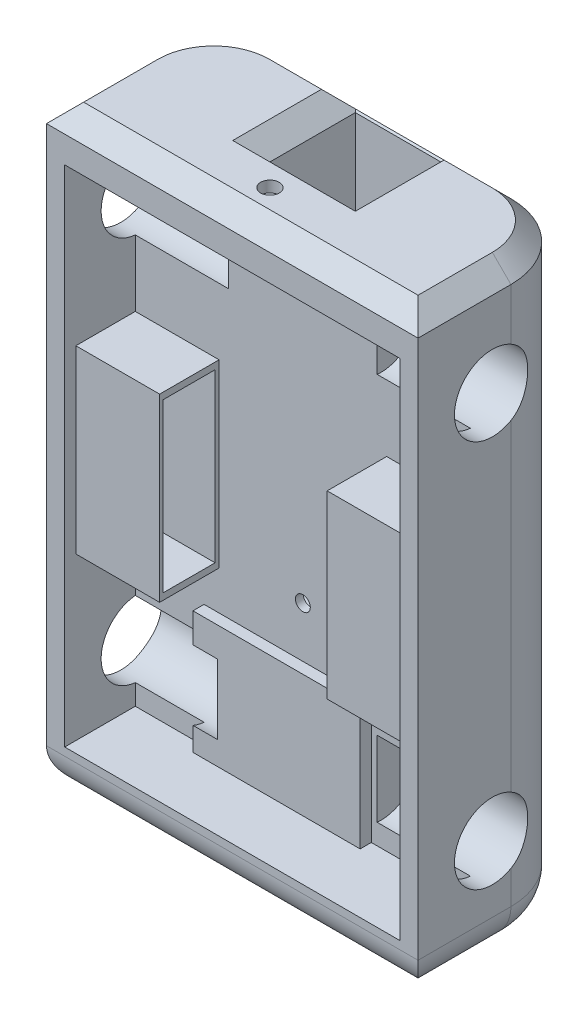
SolidWorks part; units mm, degrees
ref_plane "Front Plane" through (0, 0, 0) normal (0, 0, 1) x (1, 0, 0)
ref_plane "Top Plane" through (0, 0, 0) normal (0, 1, 0) x (1, 0, 0)
ref_plane "Right Plane" through (0, 0, 0) normal (1, 0, 0) x (0, 0, -1)
sketch "Sketch1" plane through (0, 0, 0) normal (0, 0, 1) x (1, 0, 0)
  line L16 (-50, 80) -> (50, 80)
  line L17 (-50, 80) -> (-50, -80)
  line L18 (-50, -80) -> (50, -80)
  line L19 (50, 80) -> (50, -80)
  line L20 (-50, 80) -> (50, -80) construction
  line L21 (-50, -80) -> (50, 80) construction
  point P0 (0, 0)
  point P3 (0, 0)
  point P6 (0, 0)
extrude "Boss-Extrude1" add sketch "Sketch1" along normal blind 20
ref_plane "Plane1" through (0, 80, 0) normal (0, 1, 0) x (1, 0, 0)
sketch "Sketch5" plane through (0, 80, 0) normal (0, 1, 0) x (1, 0, 0)
  line L1 (50, 0) -> (-50, 0)
  line L2 (50, 0) -> (50, 5)
  line L3 (30, 25) -> (-30, 25)
  line L4 (-50, 0) -> (-50, 5)
  arc A0 (-30, 25) -> (-50, 5) centre (-30, 5) ccw
  arc A1 (50, 5) -> (30, 25) centre (30, 5) ccw
  point P8 (-50, 25)
  point P11 (50, 25)
  dimension "D3" = 20
  dimension "D1" = 25
  dimension "D2" = 100
extrude "Boss-Extrude2" add sketch "Sketch5" against normal blind 160 contours A1 L3 A0 L4 L1 L2
fillet "Fillet4" radius 10 6 edges at (0, -80, 20) (50, -80, 7.5) (44.1421, -80, -19.1421) (0, -80, -25) (-44.1421, -80, -19.1421) (-50, -80, 7.5)
sketch "Sketch11" plane through (0, 0, 20) normal (0, 0, 1) x (1, 0, 0)
  line L1 (45.092, 67.8431) -> (-45.092, 67.8431)
  line L2 (45.092, 67.8431) -> (45.092, -67.8431)
  line L3 (45.092, -67.8431) -> (-45.092, -67.8431)
  line L4 (-45.092, 67.8431) -> (-45.092, -67.8431)
  line L5 (45.092, 67.8431) -> (-45.092, -67.8431) construction
  line L6 (45.092, -67.8431) -> (-45.092, 67.8431) construction
  point P0 (0, 0)
extrude "Cut-Extrude3" cut sketch "Sketch11" against normal blind 19 contours L2 L3 L4 L1
sketch "Sketch12" plane through (0, 80, 0) normal (0, 1, 0) x (1, 0, 0)
  line L0 (0, -20) -> (0, 25) construction
  line L1 (50, -20) -> (-50, -20) construction
  line L2 (30, 25) -> (-30, 25) construction
  line L3 (50, 2.5) -> (-50, 2.5) construction
  line L4 (50, -20) -> (50, 5) construction
  line L5 (-50, -20) -> (-50, 5) construction
  line L11 (12, 1.1277) -> (-11, 1.1277)
  line L12 (12, 1.1277) -> (12, 24.1277)
  line L13 (12, 24.1277) -> (-11, 24.1277)
  line L14 (-11, 1.1277) -> (-11, 24.1277)
  line L15 (12, 1.1277) -> (-11, 24.1277) construction
  line L16 (12, 24.1277) -> (-11, 1.1277) construction
  point P13 (0.5, 12.6277)
  dimension "D1" = 23
  dimension "D2" = 23
extrude "Cut-Extrude4" cut sketch "Sketch12" against normal blind 110 contours L12 L13 L14 L11
sketch "Sketch13" plane through (0, 0, -25) normal (0, 0, -1) x (-1, 0, 0)
  line L0 (0, 0) -> (0, 80) construction
  line L1 (26.3419, 80) -> (-26.3419, 80) construction
  line L2 (0, 0) -> (30, 0) construction
  line L3 (30, -70) -> (30, 80) construction
  ellipse E0 centre (0, 40) end of major axis (0, 24.536) minor radius 8.1947
extrude "Cut-Extrude5" cut sketch "Sketch13" against normal blind 4
sketch "Sketch14" plane through (50, 0, 0) normal (1, 0, 0) x (0, 0, -1)
  line L0 (0, -52.1971) -> (0, 0) construction
  line L5 (-20, 0) -> (0, 0) construction
  line L6 (-20, -70) -> (-20, 80) construction
  line L7 (0, -35) -> (-20, -35) construction
  circle A0 centre (0, -52.1971) radius 10.2
  circle A1 centre (0, 52.1971) radius 10.2
sketch "Sketch15" plane through (0, 0, -1.1277) normal (0, 0, -1) x (-1, 0, 0)
  circle A0 centre (0, -21.2748) radius 2
extrude "Cut-Extrude6" cut sketch "Sketch15" against normal blind 4
sketch "Sketch17" plane through (-50, 0, 0) normal (-1, 0, 0) x (0, 0, 1)
  line L0 (0, 0) -> (0, -52.1653) construction
  line L2 (20, 0) -> (0, 0) construction
  line L3 (20, 80) -> (20, -70) construction
  line L4 (0, -35) -> (20, -35) construction
  circle A0 centre (0, -52.1653) radius 10.2
  circle A1 centre (0, 52.1653) radius 10.2
chamfer "Chamfer1" distance 5 angle 45 10 edges at (12, 80, -12.6277) (0.5, 80, -24.1277) (-11, 80, -12.6277) (0.5, 80, -1.1277) (0, 80, 20) (-50, 80, 7.5) (-44.1421, 80, -19.1421) (0, 80, -25) (44.1421, 80, -19.1421) (50, 80, 7.5)
sketch "Sketch22" plane through (0, 0, 1) normal (0, 0, 1) x (1, 0, 0)
  line L0 (-45.092, 0) -> (0, 0) construction
  line L1 (-45.092, 67.8431) -> (-45.092, -67.8431) construction
  line L2 (0, 0) -> (0, -67.8431) construction
  line L3 (45.092, -67.8431) -> (-45.092, -67.8431) construction
  line L4 (-22.546, 0) -> (-22.546, -67.8431) construction
  line L7 (45.092, -67.8431) -> (-45.092, -67.8431) construction
  line L9 (-45.092, 67.8431) -> (-45.092, -67.8431) construction
  line L10 (-22.546, -24.3531) -> (-45.092, -24.3531)
  line L11 (-22.546, -24.3531) -> (-22.546, 24.1793)
  line L12 (-22.546, 24.1793) -> (-45.092, 24.1793)
  line L13 (-45.092, -24.3531) -> (-45.092, 24.1793)
  line L14 (22.546, -24.3531) -> (22.546, 24.1793)
  line L15 (22.546, 24.1793) -> (45.092, 24.1793)
  line L16 (45.092, -24.3531) -> (45.092, 24.1793)
  line L17 (22.546, -24.3531) -> (45.092, -24.3531)
extrude "Boss-Extrude7" add sketch "Sketch22" along normal blind 16
sketch "Sketch23" plane through (-22.546, 0, 0) normal (1, 0, 0) x (0, 0, -1)
  line L1 (-16.0703, -22.5997) -> (-2.0703, -22.5997)
  line L2 (-16.0703, -22.5997) -> (-16.0703, 22.4003)
  line L3 (-16.0703, 22.4003) -> (-2.0703, 22.4003)
  line L4 (-2.0703, -22.5997) -> (-2.0703, 22.4003)
  line L5 (-16.0703, -22.5997) -> (-2.0703, 22.4003) construction
  line L6 (-16.0703, 22.4003) -> (-2.0703, -22.5997) construction
  point P0 (-9.0703, -0.0997)
  dimension "D1" = 14
  dimension "D2" = 45
sketch "Sketch24" plane through (22.546, 0, 0) normal (-1, 0, 0) x (0, 0, 1)
  line L1 (16.1432, 22.651) -> (2.1432, 22.651)
  line L2 (16.1432, 22.651) -> (16.1432, -22.349)
  line L3 (16.1432, -22.349) -> (2.1432, -22.349)
  line L4 (2.1432, 22.651) -> (2.1432, -22.349)
  line L5 (16.1432, 22.651) -> (2.1432, -22.349) construction
  line L6 (16.1432, -22.349) -> (2.1432, 22.651) construction
  point P0 (9.1432, 0.151)
  dimension "D1" = 45
  dimension "D2" = 14
sketch "Sketch26" plane through (0, 0, 1) normal (0, 0, 1) x (1, 0, 0)
  line L0 (45.092, -67.8431) -> (-45.092, -67.8431) construction
  line L1 (-26.5838, -67.8431) -> (18.4162, -67.8431)
  line L2 (-26.5838, -67.8431) -> (-26.5838, -34.8431)
  line L3 (-26.5838, -34.8431) -> (18.4162, -34.8431)
  line L4 (18.4162, -67.8431) -> (18.4162, -34.8431)
  dimension "D1" = 45
  dimension "D2" = 33
extrude "Boss-Extrude8" add sketch "Sketch26" along normal blind 3
sketch "Sketch27" plane through (0, -80, 0) normal (0, -1, 0) x (1, 0, 0)
  line L0 (-40, 2.5) -> (40, 2.5) construction
  line L1 (-40, 10) -> (-40, -5) construction
  line L2 (40, -5) -> (40, 10) construction
  line L3 (0, 2.5) -> (0, 10) construction
  line L4 (40, 10) -> (-40, 10) construction
  line L5 (0, 2.5) -> (25, 2.5) construction
  line L6 (0, 2.5) -> (-25, 2.5) construction
  circle A0 centre (0, 2.5) radius 4
  circle A2 centre (-25, 2.5) radius 4
  circle A3 centre (25, 2.5) radius 4
  dimension "D1" = 2
  dimension "D2" = 25
  dimension "D4" = 25
  dimension "D3" = 2
extrude "Cut-Extrude13" cut sketch "Sketch27" against normal blind 3
ref_plane "Plane2" through (0, 0, 20) normal (0, 0, 1) x (1, 0, 0)
sketch "Sketch28" plane through (0, 80, 0) normal (0, 1, 0) x (1, 0, 0)
  circle A0 centre (0, -9.8535) radius 2.5067
extrude "Cut-Extrude14" cut sketch "Sketch28" against normal blind 3
extrude "Cut-Extrude15" cut sketch "Sketch14" against normal blind 30
extrude "Cut-Extrude16" cut sketch "Sketch17" against normal blind 30
extrude "Cut-Extrude17" cut sketch "Sketch23" against normal blind 20
extrude "Cut-Extrude18" cut sketch "Sketch24" against normal blind 20
